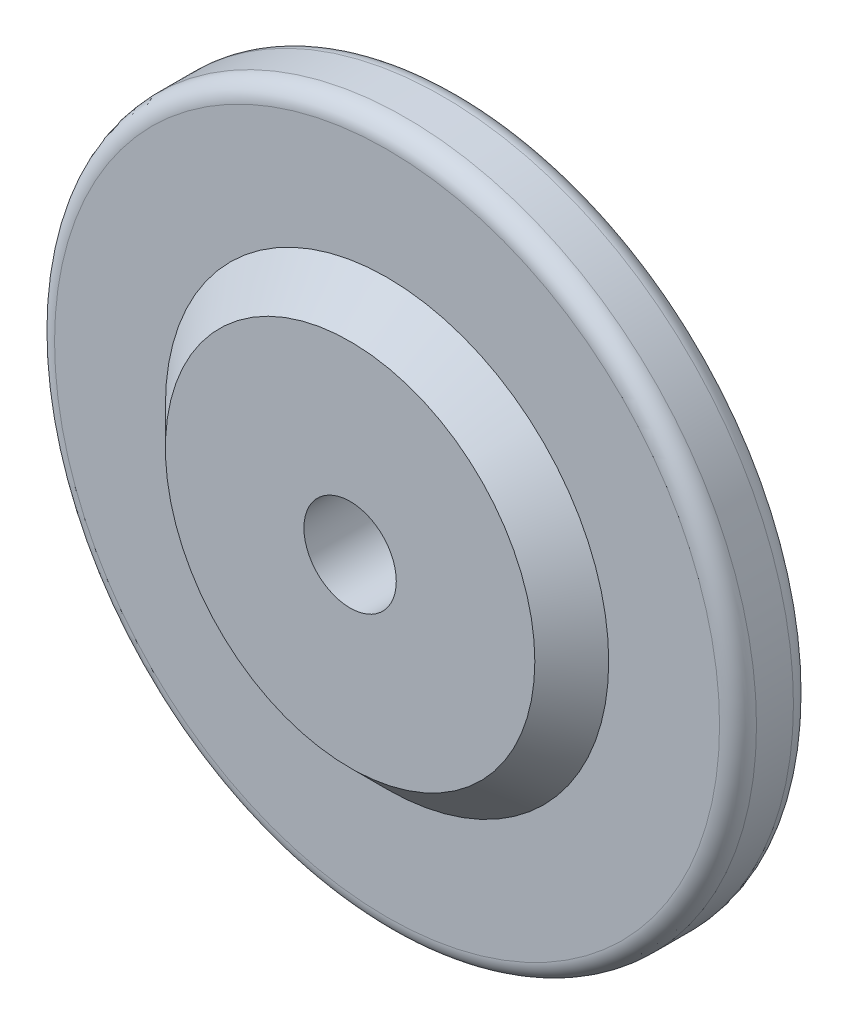
SolidWorks part; units mm, degrees
material "Natural Rubber"
ref_plane "Front Plane" through (0, 0, 0) normal (0, 0, 1) x (1, 0, 0)
ref_plane "Top Plane" through (0, 0, 0) normal (0, 1, 0) x (1, 0, 0)
ref_plane "Right Plane" through (0, 0, 0) normal (1, 0, 0) x (0, 0, -1)
sketch "Sketch1" plane through (0, 0, 0) normal (0, 0, 1) x (1, 0, 0)
  circle A0 centre (0, 0) radius 9.5
  circle A1 centre (0, 0) radius 1.25
  circle A2 centre (0, 0) radius 6
  dimension "D1" = 12
  dimension "D2" = 2.5
  dimension "D3" = 19
extrude "Boss-Extrude1" add sketch "Sketch1" along normal blind 2 contours A0 A2 | A2 A1 region at (-9.2313, 0, 0) region at (-5.8303, 0, 0)
extrude "Boss-Extrude2" add sketch "Sketch1<3>" along normal blind 1 draft 45 from surface contours A1 | A2 A1 region at (0, 0, 0) region at (-5.8303, 0, 0) starting at face at (9.5, 0, 2)
sketch "Sketch1<3>" plane through (0, 0, 0) normal (0, 0, 1) x (1, 0, 0) same geometry as "Sketch1"
sketch "Sketch2" plane through (0, 0, 0) normal (0, 0, -1) x (-1, 0, 0)
  circle A0 centre (0, 0) radius 8.5
  dimension "D1" = 17
extrude "Cut-Extrude1" cut sketch "Sketch2" against normal blind 0.25 draft 84
extrude "Cut-Extrude2" cut sketch "Sketch1<4>" along normal blind 40.25 contours A1 region at (0, 0, 0)
sketch "Sketch1<4>" plane through (0, 0, 0) normal (0, 0, 1) x (1, 0, 0) same geometry as "Sketch1"
fillet "Fillet1" radius 0.5 2 edges at (9.5, 0, 0) (9.5, 0, 2)
